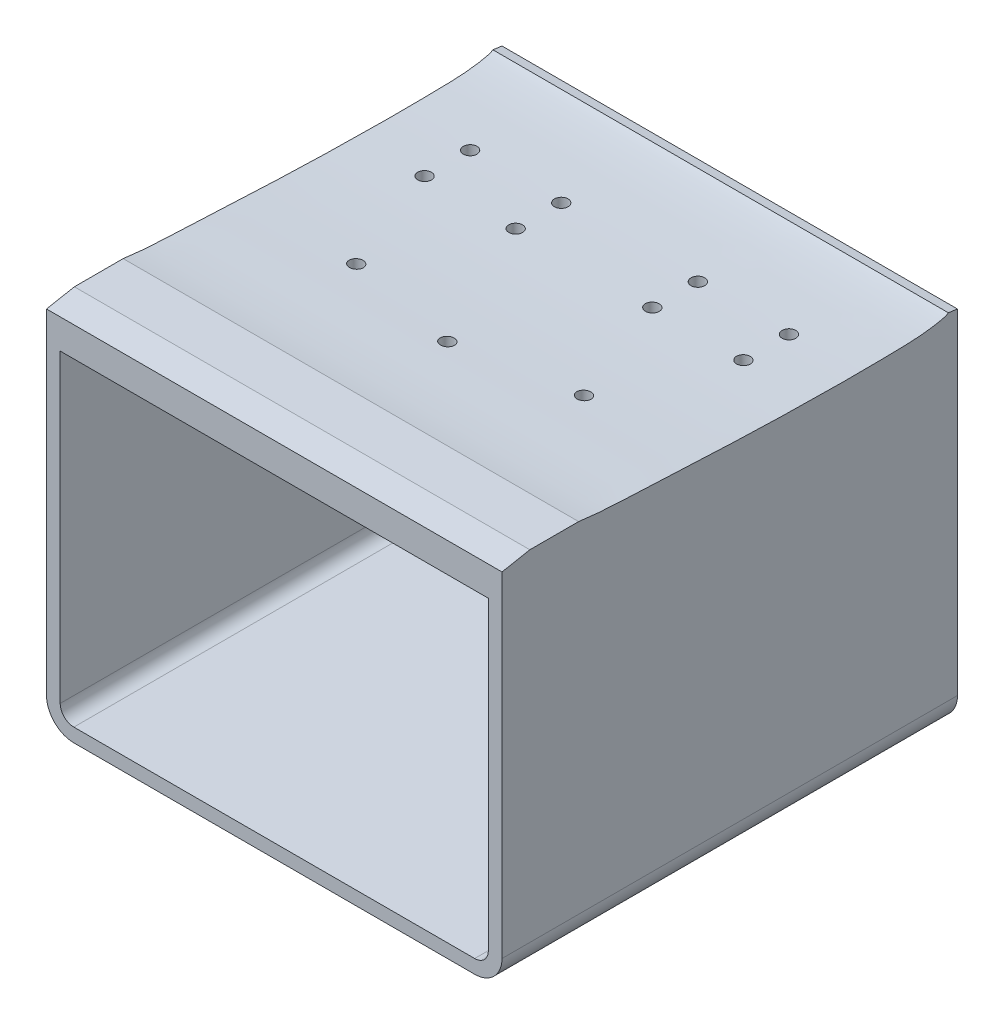
SolidWorks part; units mm, degrees
ref_plane "Front Plane" through (0, 0, 0) normal (0, 0, 1) x (1, 0, 0)
ref_plane "Top Plane" through (0, 0, 0) normal (0, 1, 0) x (1, 0, 0)
ref_plane "Right Plane" through (0, 0, 0) normal (1, 0, 0) x (0, 0, -1)
sketch "Sketch1" plane through (0, 0, 0) normal (0, 0, 1) x (1, 0, 0)
  line L1 (-44, -41) -> (44, -41)
  line L2 (-50, -35) -> (-50, 35)
  line L3 (-50, 35) -> (50, 35)
  line L4 (50, -35) -> (50, 35)
  line L5 (0, 35) -> (0, -41) construction
  line L6 (-50, 0) -> (50, 0) construction
  arc A0 (44, -41) -> (50, -35) centre (44, -35) ccw
  arc A1 (-44, -41) -> (-50, -35) centre (-44, -35) cw
  point P0 (0, 0)
  point P9 (-50, -41)
  dimension "D3" = 6
  dimension "D1" = 100
  dimension "D2" = 70
extrude "Boss-Extrude1" add sketch "Sketch1" along normal mid plane 100
shell "Shell1" thickness 3 removed face at (0, -14.0809, 50) removed face at (0, -14.0809, -50)
sketch "Sketch2" plane through (0, 0, 0) normal (1, 0, 0) x (0, 0, -1)
  line L0 (-50, 35) -> (50, 35) construction
  line L1 (-50, 35) -> (50, 35)
  line L2 (50, 35) -> (50, 38.5)
  line L3 (-50, 38.5) -> (50, 38.5) construction
  line L4 (-33.1753, 39.6612) -> (47.993, 38.7829) construction
  line L5 (7.4088, 39.2221) -> (7.4088, 47.0302) construction
  line L6 (47.993, 38.7829) -> (47.993, 38.5) construction
  line L7 (0, 38.5) -> (0, 47.9) construction
  line L8 (-50, 38.5) -> (-50, 35)
  line L9 (-33.1753, 39.6612) -> (-43.8867, 39.6612)
  line L10 (47.993, 38.7829) -> (50, 38.5)
  spline S0 degree 3 poles (-50, 38.5) (-43.2434, 39.4638) (-33.3725, 37.1687) (-19.9976, 36.7405) (-10.0025, 36.1774) (-0.0016, 35.7503) (9.9976, 35.3817) (18.3331, 35.2663) (24.9997, 35.1643) (30.0003, 35.182) (35.0003, 35.2477) (39.3373, 35.3168) (42.6742, 35.539) (45.0113, 35.8488) (46.6755, 36.1847) (48.0382, 36.5212) (49.227, 37.1175) (49.9633, 37.8039) (50, 38.5) knots 0 0 0 0 0.198457 0.297484 0.39647 0.495427 0.594346 0.693224 0.742658 0.792089 0.841524 0.890971 0.920709 0.940661 0.960825 0.971091 0.982144 1 1 1 1
  spline S1 degree 3 poles (50, 38.5) (50.0205, 39.712) (49.3256, 41.3572) (48.0944, 43.2839) (46.7718, 44.8024) (45.1061, 46.2408) (42.7739, 47.7643) (39.4473, 49.2172) (35.068, 50.3315) (30.0087, 50.7559) (24.9963, 50.7188) (18.3183, 50.3576) (9.9695, 49.4743) (-0.0248, 47.9479) (-10.0084, 46.1112) (-19.9994, 44.1967) (-33.3338, 41.6689) (-43.3331, 39.7656) (-50, 38.5) knots 0 0 0 0 0.032627 0.049883 0.064276 0.089251 0.111668 0.142584 0.191136 0.23834 0.285329 0.332382 0.426847 0.521876 0.617364 0.713023 0.808682 1 1 1 1
  spline S2 degree 3 poles (47.993, 38.7829) (47.8183, 38.6591) (47.6288, 38.5565) (47.2377, 38.3938) (47.0332, 38.3367) (46.6203, 38.2333) (46.413, 38.1866) (45.9979, 38.095) (45.7901, 38.0513) (44.7487, 37.8435) (43.9088, 37.7152) (42.2181, 37.5228) (41.3718, 37.4578) (39.6782, 37.362) (38.8309, 37.3305) (37.1359, 37.2841) (36.2881, 37.2695) (34.5925, 37.2439) (33.7446, 37.2321) (31.201, 37.1996) (29.5051, 37.1825) (26.1126, 37.1715) (24.4168, 37.1807) (21.0255, 37.2229) (19.3301, 37.2497) (15.9391, 37.3008) (14.2436, 37.3281) (10.853, 37.3971) (9.1579, 37.4401) (4.0732, 37.5964) (0.684, 37.7304) (-4.3994, 37.9424) (-6.0937, 38.0166) (-9.4817, 38.1751) (-11.1753, 38.261) (-14.5622, 38.4367) (-16.2556, 38.5256) (-18.7964, 38.648) (-19.6434, 38.6868) (-21.3378, 38.7597) (-22.185, 38.7945) (-24.7264, 38.9067) (-26.42, 38.9918) (-28.9565, 39.188) (-29.8012, 39.2658) (-31.4891, 39.449) (-32.3323, 39.5527) (-33.1753, 39.6612) knots 0 0 0 0 0.007813 0.007813 0.015625 0.015625 0.023438 0.023438 0.03125 0.03125 0.0625 0.0625 0.09375 0.09375 0.125 0.125 0.15625 0.15625 0.1875 0.1875 0.25 0.25 0.3125 0.3125 0.375 0.375 0.4375 0.4375 0.5 0.5 0.625 0.625 0.6875 0.6875 0.75 0.75 0.8125 0.8125 0.84375 0.84375 0.875 0.875 0.9375 0.9375 0.96875 0.96875 1 1 1 1
  spline S3 degree 3 poles (-33.1753, 39.6612) (-29.6605, 40.329) (-26.1454, 40.9953) (-19.116, 42.3315) (-15.6023, 43.0053) (-8.572, 44.3367) (-5.0558, 44.9967) (1.994, 46.2214) (5.5299, 46.7835) (12.6228, 47.7382) (16.1799, 48.1325) (21.535, 48.5286) (23.3208, 48.6283) (26.8943, 48.7364) (28.682, 48.7452) (31.3669, 48.6138) (32.2614, 48.5451) (34.0337, 48.3387) (34.9131, 48.2002) (36.6552, 47.8368) (37.5182, 47.6131) (38.7989, 47.2061) (39.2247, 47.0582) (40.0637, 46.739) (40.8902, 46.396) (41.6858, 45.9945) (42.4629, 45.5577) (42.8421, 45.3218) (43.5833, 44.8168) (43.9468, 44.547) (44.6453, 43.9816) (44.9807, 43.6853) (45.6193, 43.0614) (45.9231, 42.7343) (46.4886, 42.0389) (46.7493, 41.6663) (47.1051, 41.088) (47.2182, 40.8922) (47.4342, 40.4952) (47.5367, 40.2937) (47.7214, 39.8797) (47.8038, 39.6664) (47.9308, 39.2325) (47.9758, 39.0111) (47.993, 38.7829) knots 0 0 0 0 0.125 0.125 0.25 0.25 0.375 0.375 0.5 0.5 0.625 0.625 0.6875 0.6875 0.75 0.75 0.78125 0.78125 0.8125 0.8125 0.84375 0.84375 0.859375 0.859375 0.875 0.890625 0.890625 0.90625 0.90625 0.921875 0.921875 0.9375 0.9375 0.953125 0.953125 0.96875 0.96875 0.976562 0.976562 0.984375 0.984375 0.992188 0.992188 1 1 1 1
  dimension "D1" = 3.5
  dimension "D2" = 81.1682
  dimension "D3" = 7.8082
  dimension "D4" = 100
  dimension "D5" = 2.007
  dimension "D6" = 0.2829
  dimension "D7" = 9.4
extrude "Boss-Extrude3" add sketch "Sketch2" along normal through all and the other way through all contours L10 S2 L9 S1 S0 | S0 L8 L1 L2 region at (0, 36.1667, 20.4846) region at (0, 37.0898, -3.894)
sketch "Sketch4" plane through (0, 0, 0) normal (0, 1, 0) x (1, 0, 0)
  line L0 (50, 50) -> (-50, 50) construction
  line L1 (50, 50) -> (-50, 50)
  line L2 (0, 50) -> (0, -12) construction
  line L3 (-50, 28) -> (-35, 28) construction
  line L4 (-50, 47.993) -> (-50, -33.1753) construction
  line L5 (-35, 28) -> (-35, 50) construction
  line L6 (-35, 18) -> (-15, 18) construction
  line L7 (-25, 18) -> (-25, -7) construction
  circle A0 centre (0, -12) radius 1.5
  circle A1 centre (-35, 28) radius 1.5
  circle A2 centre (-15, 28) radius 1.5
  circle A3 centre (-15, 18) radius 1.5
  circle A4 centre (-35, 18) radius 1.5
  circle A5 centre (35, 18) radius 1.5
  circle A6 centre (15, 18) radius 1.5
  circle A7 centre (15, 28) radius 1.5
  circle A8 centre (35, 28) radius 1.5
  circle A9 centre (-25, -7) radius 1.5
  circle A10 centre (25, -7) radius 1.5
  dimension "D2" = 3
  dimension "D5" = 3
  dimension "D9" = 3
  dimension "D1" = 62
  dimension "D3" = 15
  dimension "D4" = 22
  dimension "D8" = 25
  dimension "D6" = 2
  dimension "D7" = 2
extrude "Cut-Extrude1" cut sketch "Sketch4" along normal through all contours A0 | A4 | A2 | A3 | A7 | A6 | A5 | A8 | A9 | A10 | A1 region at (0, 0, 12) region at (-15, 0, -28) region at (-15, 0, -18) region at (-35, 0, -18) region at (35, 0, -18) region at (15, 0, -18) region at (15, 0, -28) region at (35, 0, -28) region at (-25, 0, 7) region at (25, 0, 7)
